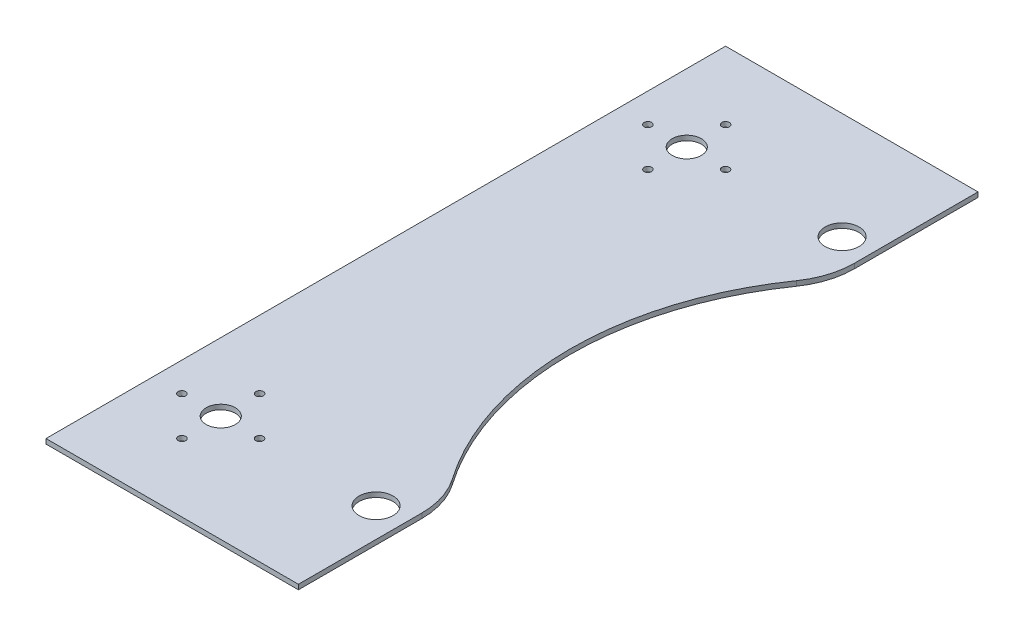
SolidWorks part; units mm, degrees
material "6061 Alloy"
ref_plane "Front Plane" through (0, 0, 0) normal (0, 0, 1) x (1, 0, 0)
ref_plane "Top Plane" through (0, 0, 0) normal (0, 1, 0) x (1, 0, 0)
ref_plane "Right Plane" through (0, 0, 0) normal (1, 0, 0) x (0, 0, -1)
sketch "Sketch1" plane through (0, 0, 0) normal (0, 1, 0) x (1, 0, 0)
  line L1 (82.55, -222.25) -> (-82.55, -222.25)
  line L2 (82.55, -222.25) -> (82.55, 222.25)
  line L3 (82.55, 222.25) -> (-82.55, 222.25)
  line L4 (-82.55, -222.25) -> (-82.55, 222.25)
  line L5 (82.55, -222.25) -> (-82.55, 222.25) construction
  line L6 (82.55, 222.25) -> (-82.55, -222.25) construction
  point P0 (0, 0)
  dimension "D1" = 165.1
  dimension "D2" = 444.5
extrude "Boss-Extrude1" add sketch "Sketch1" along normal blind 3.175
sketch "Sketch3" plane through (0, 3.175, 0) normal (0, 1, 0) x (1, 0, 0)
  arc A0 (-28.575, -152.4) -> (-47.625, -152.4) centre (-38.1, -152.4) ccw construction
  arc A1 (-47.625, -152.4) -> (-28.575, -152.4) centre (-38.1, -152.4) ccw construction
  arc A2 (-28.575, -152.4) -> (-47.625, -152.4) centre (-38.1, -152.4) ccw
  arc A3 (-47.625, -152.4) -> (-28.575, -152.4) centre (-38.1, -152.4) ccw
  arc A4 (-28.575, 152.4) -> (-47.625, 152.4) centre (-38.1, 152.4) ccw construction
  arc A5 (-47.625, 152.4) -> (-28.575, 152.4) centre (-38.1, 152.4) ccw construction
  arc A6 (-28.575, 152.4) -> (-47.625, 152.4) centre (-38.1, 152.4) ccw
  arc A7 (-47.625, 152.4) -> (-28.575, 152.4) centre (-38.1, 152.4) ccw
extrude "Cut-Extrude2" cut sketch "Sketch3" against normal through all
hole_wizard "#10 (0.1935) Diameter Hole1" positions "Sketch4" profile "Sketch5" hole size "#10" standard "ANSI Inch" end condition through all
sketch "Sketch4" plane through (0, 3.175, 0) normal (0, 1, 0) x (1, 0, 0)
  arc A0 (-36.0807, -127) -> (-40.1193, -127) centre (-38.1, -127) ccw construction
  arc A1 (-40.1193, -127) -> (-36.0807, -127) centre (-38.1, -127) ccw construction
  arc A2 (-61.4807, -152.4) -> (-65.5193, -152.4) centre (-63.5, -152.4) ccw construction
  arc A3 (-65.5193, -152.4) -> (-61.4807, -152.4) centre (-63.5, -152.4) ccw construction
  arc A4 (-36.0807, -177.8) -> (-40.1193, -177.8) centre (-38.1, -177.8) ccw construction
  arc A5 (-40.1193, -177.8) -> (-36.0807, -177.8) centre (-38.1, -177.8) ccw construction
  arc A6 (-10.6807, -152.4) -> (-14.7193, -152.4) centre (-12.7, -152.4) ccw construction
  arc A7 (-14.7193, -152.4) -> (-10.6807, -152.4) centre (-12.7, -152.4) ccw construction
  arc A8 (-36.0807, -127) -> (-40.1193, -127) centre (-38.1, -127) ccw construction
  arc A9 (-40.1193, -127) -> (-36.0807, -127) centre (-38.1, -127) ccw construction
  arc A10 (-61.4807, -152.4) -> (-65.5193, -152.4) centre (-63.5, -152.4) ccw construction
  arc A11 (-65.5193, -152.4) -> (-61.4807, -152.4) centre (-63.5, -152.4) ccw construction
  arc A12 (-36.0807, -177.8) -> (-40.1193, -177.8) centre (-38.1, -177.8) ccw construction
  arc A13 (-40.1193, -177.8) -> (-36.0807, -177.8) centre (-38.1, -177.8) ccw construction
  arc A14 (-10.6807, -152.4) -> (-14.7193, -152.4) centre (-12.7, -152.4) ccw construction
  arc A15 (-14.7193, -152.4) -> (-10.6807, -152.4) centre (-12.7, -152.4) ccw construction
  arc A16 (-10.6807, 152.4) -> (-14.7193, 152.4) centre (-12.7, 152.4) ccw construction
  arc A17 (-14.7193, 152.4) -> (-10.6807, 152.4) centre (-12.7, 152.4) ccw construction
  arc A18 (-36.0807, 177.8) -> (-40.1193, 177.8) centre (-38.1, 177.8) ccw construction
  arc A19 (-40.1193, 177.8) -> (-36.0807, 177.8) centre (-38.1, 177.8) ccw construction
  arc A20 (-61.4807, 152.4) -> (-65.5193, 152.4) centre (-63.5, 152.4) ccw construction
  arc A21 (-65.5193, 152.4) -> (-61.4807, 152.4) centre (-63.5, 152.4) ccw construction
  arc A22 (-36.0807, 127) -> (-40.1193, 127) centre (-38.1, 127) ccw construction
  arc A23 (-40.1193, 127) -> (-36.0807, 127) centre (-38.1, 127) ccw construction
  arc A24 (-10.6807, 152.4) -> (-14.7193, 152.4) centre (-12.7, 152.4) ccw
  arc A25 (-14.7193, 152.4) -> (-10.6807, 152.4) centre (-12.7, 152.4) ccw
  arc A26 (-36.0807, 177.8) -> (-40.1193, 177.8) centre (-38.1, 177.8) ccw
  arc A27 (-40.1193, 177.8) -> (-36.0807, 177.8) centre (-38.1, 177.8) ccw
  arc A28 (-61.4807, 152.4) -> (-65.5193, 152.4) centre (-63.5, 152.4) ccw
  arc A29 (-65.5193, 152.4) -> (-61.4807, 152.4) centre (-63.5, 152.4) ccw
  arc A30 (-36.0807, 127) -> (-40.1193, 127) centre (-38.1, 127) ccw
  arc A31 (-40.1193, 127) -> (-36.0807, 127) centre (-38.1, 127) ccw
  point P0 (-38.1, -177.8)
  point P2 (-63.5, -152.4)
  point P4 (-38.1, -127)
  point P6 (-12.7, -152.4)
  point P44 (-38.1, 177.8)
  point P50 (-63.5, 152.4)
  point P56 (-38.1, 127)
  point P68 (-12.7, 152.4)
sketch "Sketch5" plane through (-38.1, 3.175, 177.8) normal (1, 0, 0) x (0, 0, 1)
  line L0 (0, 0) -> (0, 3.175)
  line L1 (0, 3.175) -> (2.4574, 3.175)
  line L2 (2.4574, 3.175) -> (2.4574, 0)
  line L5 (2.4574, 0) -> (0, 0)
  line L11 (0, -6.35) -> (0, 107.95) construction
  dimension "Thru Hole Dia." = 4.9149
  dimension "Thru Hole Depth" = 3.175
sketch "Sketch6" plane through (0, 3.175, 0) normal (0, 1, 0) x (1, 0, 0)
  line L0 (-38.1, -114.3) -> (-38.1, 114.3) construction
  line L1 (63.5, -152.4) -> (-38.1, -152.4) construction
  line L2 (63.5, 152.4) -> (-38.1, 152.4) construction
  line L3 (63.5, 152.4) -> (82.55, 152.4) construction
  line L4 (82.55, -222.25) -> (82.55, 222.25) construction
  circle A0 centre (-38.1, -152.4) radius 38.1 construction
  circle A1 centre (-38.1, 152.4) radius 38.1 construction
  circle A2 centre (63.5, -152.4) radius 38.1 construction
  circle A3 centre (63.5, 152.4) radius 38.1 construction
  dimension "D1" = 76.2
  dimension "D2" = 228.6
  dimension "D3" = 101.6
  dimension "D4" = 19.05
sketch "Sketch7" plane through (0, 3.175, 0) normal (0, 1, 0) x (1, 0, 0)
  circle A0 centre (63.5, -152.4) radius 11.1125
  circle A1 centre (63.5, 152.4) radius 11.1125
  dimension "D1" = 22.225
extrude "Cut-Extrude3" cut sketch "Sketch7" against normal through all
sketch "Sketch8" plane through (0, 3.175, 0) normal (0, 1, 0) x (1, 0, 0)
  line L0 (82.55, 222.25) -> (82.55, 141.5637)
  line L1 (82.55, -222.25) -> (82.55, 222.25) construction
  line L2 (82.55, -141.5637) -> (82.55, -222.25)
  line L3 (82.55, -222.25) -> (95.25, -222.25)
  line L4 (95.25, -222.25) -> (95.25, 222.25)
  line L5 (95.25, 222.25) -> (82.55, 222.25)
  arc A0 (82.55, 141.5637) -> (73.4321, 112.525) centre (31.75, 141.5637) cw
  arc A1 (73.4321, 112.525) -> (73.4321, -112.525) centre (234.95, 0) ccw
  arc A2 (73.4321, -112.525) -> (82.55, -141.5637) centre (31.75, -141.5637) cw
  point P11 (73.4164, 112.6118)
  dimension "D2" = 50.8
  dimension "D3" = 196.85
  dimension "D4" = 152.4
  dimension "D1" = 12.7
extrude "Cut-Extrude4" cut sketch "Sketch8" against normal through all
